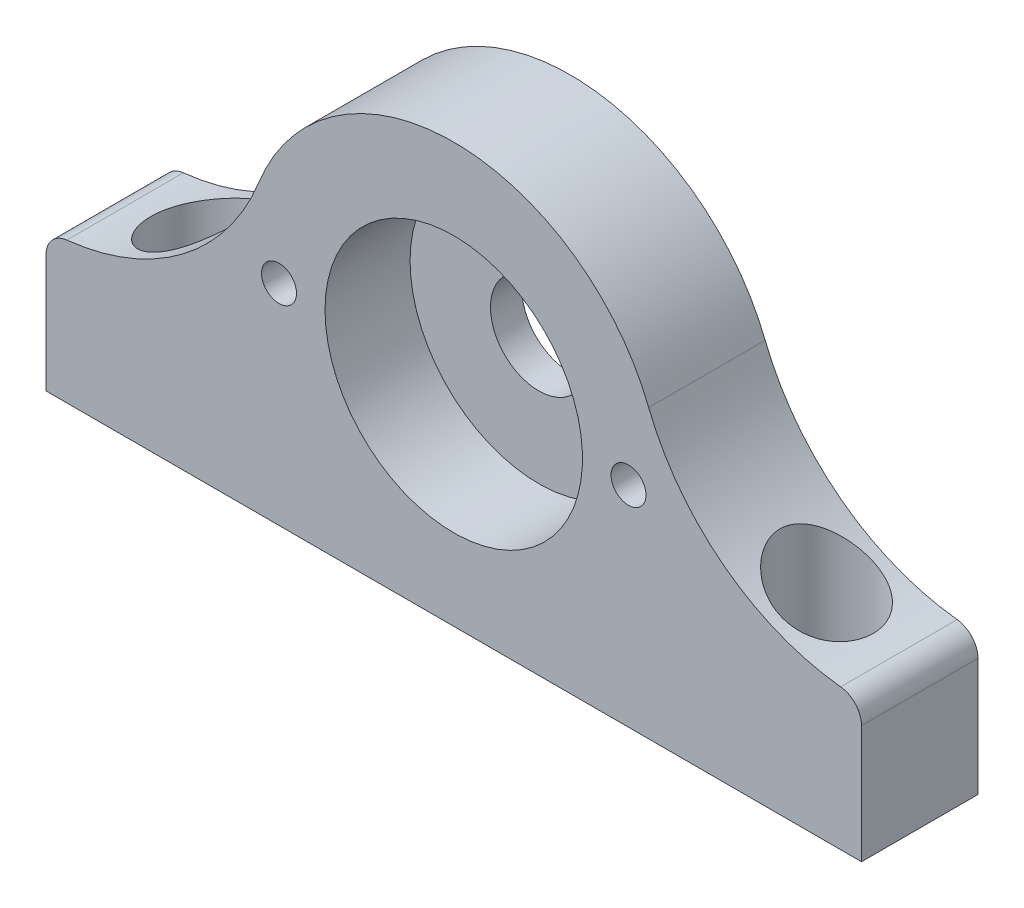
SolidWorks part; units mm, degrees
ref_plane "Front Plane" through (0, 0, 0) normal (0, 0, 1) x (1, 0, 0)
ref_plane "Top Plane" through (0, 0, 0) normal (0, 1, 0) x (1, 0, 0)
ref_plane "Right Plane" through (0, 0, 0) normal (1, 0, 0) x (0, 0, -1)
sketch "Sketch1" plane through (0, 0, 0) normal (0, 0, 1) x (1, 0, 0)
  line L0 (0, 12) -> (18.0294, 12)
  line L1 (0, 0) -> (70, 0)
  line L2 (0, 0) -> (0, 12)
  line L4 (70, 0) -> (70, 12)
  line L6 (51.9706, 12) -> (70, 12)
  arc A0 (18.0294, 12) -> (51.9706, 12) centre (35, 18) cw
  dimension "D4" = 18
  dimension "D1" = 70
  dimension "D2" = 12
  dimension "D3" = 35
  dimension "D6" = 18
extrude "Boss-Extrude1" add sketch "Sketch1" along normal blind 10
fillet "Fillet1" radius 20 2 edges at (18.0294, 12, 5) (51.9706, 12, 5)
sketch "Sketch2" plane through (0, 0, 0) normal (0, 0, 1) x (1, 0, 0)
  line L0 (70, 0) -> (70, 12) construction
  line L1 (5.5, 0) -> (-5.5, 0) construction
  circle A0 centre (35, 18) radius 11.05
  dimension "D1" = 22.1
  dimension "D2" = 35
  dimension "D3" = 18
extrude "Cut-Extrude1" cut sketch "Sketch2" against normal blind 7.3 from surface starting at face at (35, 13.1824, 10)
sketch "Sketch5" plane through (0, 0, 0) normal (0, 0, 1) x (1, 0, 0)
  line L0 (5.5, 0) -> (-5.5, 0) construction
  line L1 (70, 0) -> (70, 12) construction
  circle A0 centre (35, 18) radius 4.15
  dimension "D1" = 8.3
  dimension "D2" = 18
  dimension "D3" = 35
extrude "Cut-Extrude2" cut sketch "Sketch5" along normal blind 10
fillet "Fillet2" radius 2 2 edges at (70, 12, 5) (0, 12, 5)
sketch "Sketch6" plane through (0, 0, 0) normal (0, 1, 0) x (1, 0, 0)
  line L0 (70, 0) -> (70, -10) construction
  line L1 (0, -5.5) -> (0, 5.5) construction
  line L2 (1.7884, -10) -> (18.2656, -10) construction
  line L3 (51.7344, -10) -> (68.2116, -10) construction
  circle A0 centre (8, -5) radius 4
  circle A1 centre (62, -5) radius 4
  dimension "D1" = 8
  dimension "D2" = 8
  dimension "D3" = 8
  dimension "D4" = 8
  dimension "D5" = 5
  dimension "D6" = 5
extrude "Cut-Extrude3" cut sketch "Sketch6" along normal blind 13 from offset 4
sketch "Sketch7" plane through (0, 0, 0) normal (0, 1, 0) x (1, 0, 0)
  circle A0 centre (8, -5) radius 2
  circle A1 centre (62, -5) radius 2
  dimension "D1" = 4
  dimension "D2" = 4
extrude "Cut-Extrude4" cut sketch "Sketch7" along normal blind 13
sketch "Sketch9" plane through (0, 0, 0) normal (0, 0, 1) x (1, 0, 0)
  line L0 (0, -5.5) -> (0, 5.5) construction
  line L1 (70, 0) -> (70, 10.1208) construction
  line L2 (5.5, 0) -> (-5.5, 0) construction
  circle A0 centre (20, 18) radius 1.5
  circle A1 centre (50, 18) radius 1.5
  dimension "D5" = 3
  dimension "D1" = 20
  dimension "D2" = 20
  dimension "D3" = 18
  dimension "D4" = 18
extrude "Cut-Extrude5" cut sketch "Sketch9" against normal blind 7.5 from surface starting at face at (23.95, 18, 10)
